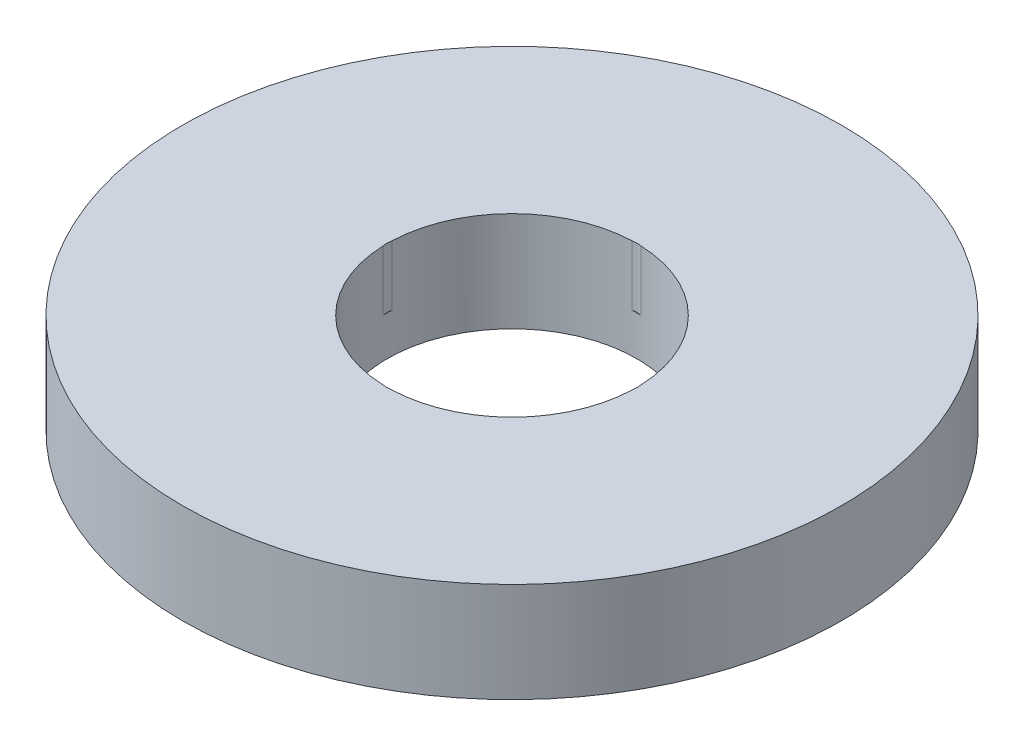
SolidWorks part; units mm, degrees
ref_plane "Front Plane" through (0, 0, 0) normal (0, 0, 1) x (1, 0, 0)
ref_plane "Top Plane" through (0, 0, 0) normal (0, 1, 0) x (1, 0, 0)
ref_plane "Right Plane" through (0, 0, 0) normal (1, 0, 0) x (0, 0, -1)
sketch "Sketch1" plane through (0, 0, 0) normal (0, 1, 0) x (1, 0, 0)
  circle A0 centre (0, 0) radius 92.5
  dimension "FLANGE_OD" = 185
extrude "Boss-Extrude1" add sketch "Sketch1" along normal blind 28
sketch "Sketch2" plane through (0, 0, 0) normal (0, 1, 0) x (1, 0, 0)
  circle A0 centre (0, 0) radius 35
  dimension "BORE_D" = 70
extrude "Cut-Extrude1" cut sketch "Sketch2" along normal through all
sketch "Sketch3" plane through (0, 28, 0) normal (0, 1, 0) x (1, 0, 0)
  circle A0 centre (0, 0) radius 27.5735 construction
  circle A1 centre (-27.5735, 0) radius 7.5082
  dimension "BOLT_D" = 15.0163
  dimension "BOLT_PCD" = 55.147
extrude "Cut-Extrude2" cut sketch "Sketch3" against normal blind 16.8546
pattern_circular "CirPattern1" count 4 over 360 about axis through (0, 0, 0) along (0, 1, 0) of "Cut-Extrude2"
